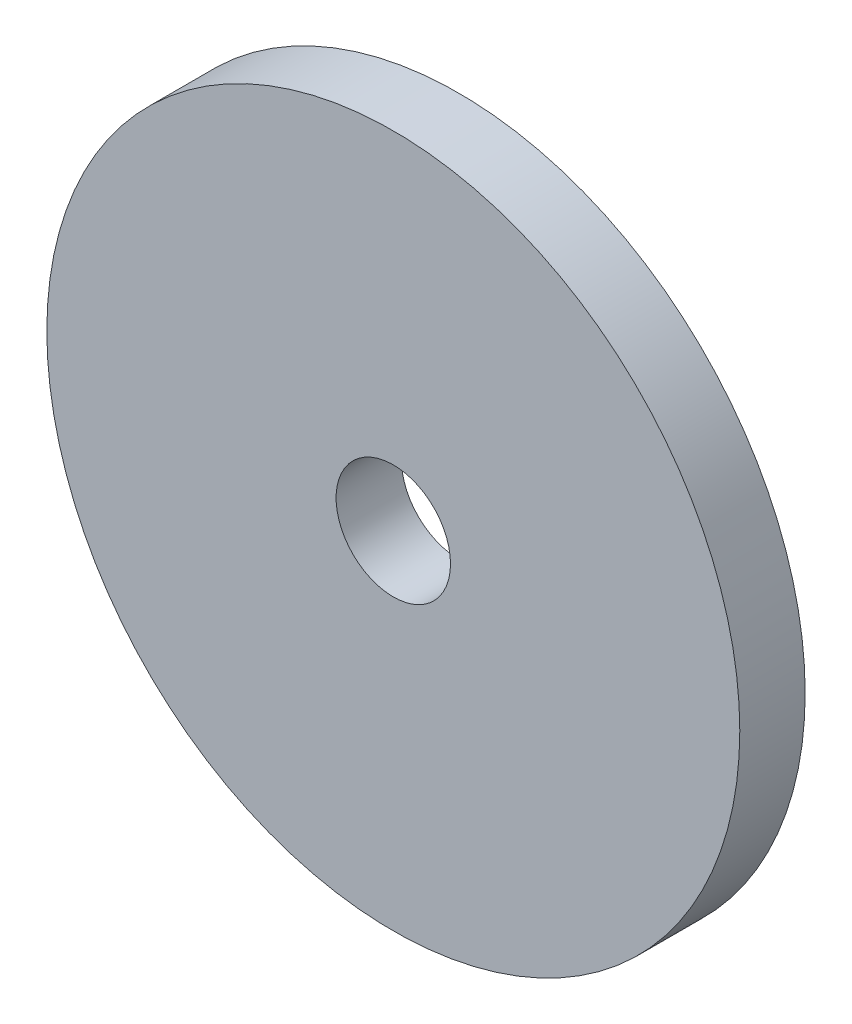
SolidWorks part; units mm, degrees
ref_plane "Plano frontal" through (0, 0, 0) normal (0, 0, 1) x (1, 0, 0)
ref_plane "Plano superior" through (0, 0, 0) normal (0, 1, 0) x (1, 0, 0)
ref_plane "Plano direito" through (0, 0, 0) normal (1, 0, 0) x (0, 0, -1)
sketch "Esboço1" plane through (0, 0, 0) normal (0, 0, 1) x (1, 0, 0)
  circle A0 centre (0, 0) radius 21.2
  circle A1 centre (0, 0) radius 3.5
  dimension "D1" = 42.4
  dimension "D2" = 7
extrude "Ressalto-extrusão1" add sketch "Esboço1" along normal blind 4
